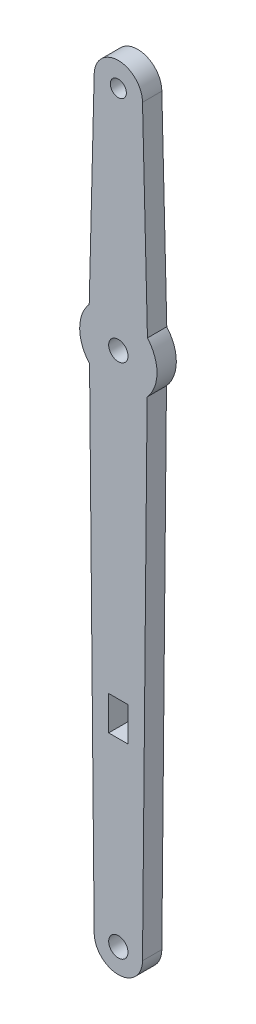
SolidWorks part; units mm, degrees
ref_plane "Plan de face" through (0, 0, 0) normal (0, 0, 1) x (1, 0, 0)
ref_plane "Plan de dessus" through (0, 0, 0) normal (0, 1, 0) x (1, 0, 0)
ref_plane "Plan de droite" through (0, 0, 0) normal (1, 0, 0) x (0, 0, -1)
sketch "Esquisse1" plane through (0, 0, 0) normal (0, 0, 1) x (1, 0, 0)
  line L0 (203.018, 987.6887) -> (203.018, 864.6887) construction
  line L1 (198.3089, 952.5089) -> (199.0768, 983.7931)
  line L2 (207.3448, 952.5089) -> (206.5768, 983.7931)
  line L3 (202.8268, 983.7931) -> (202.8268, 838.667) construction
  line L4 (198.3607, 944.5541) -> (199.0768, 868.4244)
  line L5 (207.2944, 944.5556) -> (206.5768, 868.4244)
  line L7 (201.3268, 901.7244) -> (204.3268, 901.7244)
  line L8 (201.3268, 901.7244) -> (201.3268, 896.4244)
  line L9 (201.3268, 896.4244) -> (204.3268, 896.4244)
  line L10 (204.3268, 901.7244) -> (204.3268, 896.4244)
  circle A0 centre (202.8268, 983.7931) radius 1.25
  circle A1 centre (202.8268, 983.7931) radius 3.75 construction
  circle A2 centre (202.8268, 948.5607) radius 1.5
  circle A3 centre (202.8268, 948.5607) radius 6 construction
  circle A4 centre (202.8268, 868.4244) radius 3.75 construction
  circle A5 centre (202.8268, 868.4244) radius 1.5
  arc A6 (199.0768, 983.7931) -> (206.5768, 983.7931) centre (202.8268, 983.7931) cw
  arc A7 (198.3607, 944.5541) -> (198.3089, 952.5089) centre (202.8268, 948.5607) cw
  arc A8 (207.3448, 952.5089) -> (207.2944, 944.5556) centre (202.8268, 948.5607) cw
  arc A9 (199.0768, 868.4244) -> (206.5768, 868.4244) centre (202.8268, 868.4244) ccw
  dimension "D2" = 2.5
  dimension "D3" = 7.5
  dimension "D4" = 12
  dimension "D5" = 3
  dimension "D10" = 7.5
  dimension "D11" = 3
  dimension "D20" = 198.3089
  dimension "D1" = 123
  dimension "D6" = 1.406
  dimension "D7" = 1.406
  dimension "D8" = 0.539
  dimension "D9" = 0.54
  dimension "D12" = 202.8268
  dimension "D13" = 868.4244
  dimension "D14" = 948.5607
  dimension "D15" = 983.7931
  dimension "D16" = 5.3
  dimension "D17" = 3
  dimension "D18" = 1.5
  dimension "D19" = 26.5
  dimension "D21" = 199.0768
base flange "Tôle de base pliée1" sketch "Esquisse1" thickness 3 reverse thickness direction no parameters "D1"=1.5
sketch "Lignes de pliage1" [suppressed] plane through (0, 0, 0) normal (0, 1, 0) x (1, 0, 0)
sketch "Cube de visualisation1" [suppressed] plane through (0, 0, 0) normal (0, 1, 0) x (1, 0, 0)
sheet metal parameters "Tôlerie1" thickness 3 parameters "D1"=1.5
flat pattern "Etat déplié1" [suppressed]
sketch "Lignes de pliage2" plane through (0, 0, 0) normal (0, 1, 0) x (1, 0, 0)
sketch3d "Cube de visualisation2" [suppressed]
  line L0 (4.9034, 39.1215, 0) -> (8.3518, -83.6532, 0) construction
  line L1 (-7.0917, 38.7846, 0) -> (-3.6432, -83.9901, 0) construction
  line L2 (4.9034, 39.1215, 0) -> (-7.0917, 38.7846, 0) construction
  line L3 (8.3518, -83.6532, 0) -> (-3.6432, -83.9901, 0) construction
